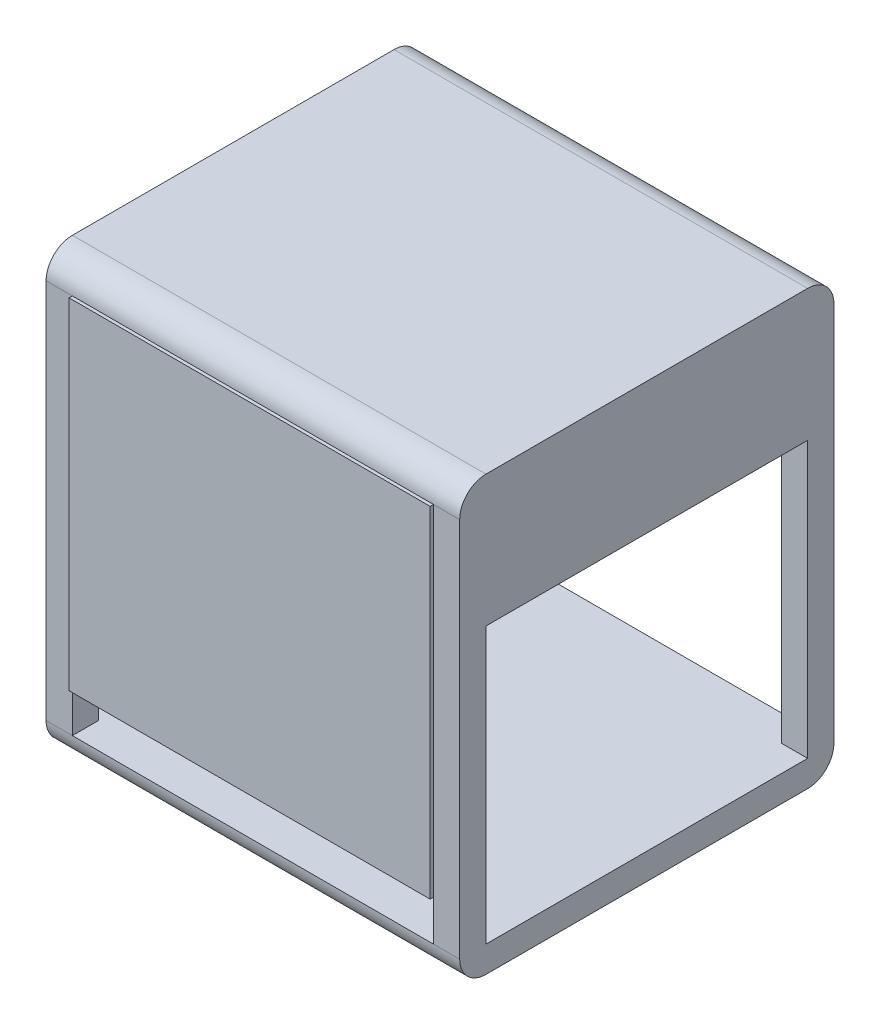
SolidWorks part; units mm, degrees
ref_plane "Front Plane" through (0, 0, 0) normal (0, 0, 1) x (1, 0, 0)
ref_plane "Top Plane" through (0, 0, 0) normal (0, 1, 0) x (1, 0, 0)
ref_plane "Right Plane" through (0, 0, 0) normal (1, 0, 0) x (0, 0, -1)
sketch "Sketch1" plane through (0, 0, 0) normal (0, 1, 0) x (1, 0, 0)
  line L1 (0, 0) -> (630, 0)
  line L2 (0, 0) -> (0, 570)
  line L3 (0, 570) -> (630, 570)
  line L4 (630, 0) -> (630, 570)
extrude "Boss-Extrude1" add sketch "Sketch1" along normal blind 660
ref_plane "Plane1" through (0, 660, 0) normal (0, 1, 0) x (1, 0, 0)
fillet "Fillet1" radius 40 4 edges at (315, 0, -570) (315, 660, -570) (315, 0, 0) (315, 660, 0)
ref_plane "Plane2" through (0, 0, 0) normal (0, 0, 1) x (1, 0, 0)
sketch "Sketch3" plane through (0, 0, 0) normal (0, 0, 1) x (1, 0, 0)
  line L4 (630, 620) -> (0, 620) construction
  line L5 (40, 620) -> (590, 620)
  line L6 (40, 620) -> (40, 40)
  line L7 (40, 40) -> (590, 40)
  line L8 (590, 620) -> (590, 40)
  line L9 (0, 40) -> (630, 40) construction
extrude "Cut-Extrude1" cut sketch "Sketch3" against normal blind 5000 and the other way blind 660
ref_plane "Plane3" through (630, 0, 0) normal (1, 0, 0) x (0, 0, -1)
sketch "Sketch4" plane through (630, 0, 0) normal (1, 0, 0) x (0, 0, -1)
  line L4 (0, 40) -> (570, 40) construction
  line L5 (40, 40) -> (530, 40)
  line L6 (40, 40) -> (40, 459.596)
  line L7 (40, 459.596) -> (530, 459.596)
  line L8 (530, 40) -> (530, 459.596)
extrude "Cut-Extrude2" cut sketch "Sketch4" against normal blind 5000 and the other way blind 5000
ref_plane "Plane4" through (0, 620, 0) normal (0, -1, 0) x (-1, 0, 0)
sketch "Sketch5" plane through (0, 620, 0) normal (0, -1, 0) x (-1, 0, 0)
  line L1 (-11.5968, 374.3051) -> (-612.9435, 374.3051)
  line L2 (-11.5968, 374.3051) -> (-11.5968, 326.7277)
  line L3 (-11.5968, 326.7277) -> (-612.9435, 326.7277)
  line L4 (-612.9435, 374.3051) -> (-612.9435, 326.7277)
extrude "Boss-Extrude2" add sketch "Sketch5" along normal blind 100
ref_plane "Plane5" through (0, 0, -326.7277) normal (0, 0, 1) x (1, 0, 0)
sketch "Sketch6" plane through (0, 0, -326.7277) normal (0, 0, 1) x (1, 0, 0)
  line L0 (590, 620) -> (40, 620) construction
  line L1 (102.7696, 620) -> (181.34, 620)
  line L2 (102.7696, 620) -> (102.7696, 316.9049)
  line L3 (102.7696, 316.9049) -> (181.34, 316.9049)
  line L4 (181.34, 620) -> (181.34, 316.9049)
extrude "Boss-Extrude3" add sketch "Sketch6" against normal blind 10 and the other way blind 50
ref_plane "Plane6" through (0, 316.9049, 0) normal (0, -1, 0) x (-1, 0, 0)
sketch "Sketch7" plane through (0, 316.9049, 0) normal (0, -1, 0) x (-1, 0, 0)
  circle A0 centre (-141.0696, 317.3682) radius 11.2487
extrude "Boss-Extrude4" add sketch "Sketch7" along normal blind 50 draft 8
ref_plane "Plane7" through (0, 0, 0) normal (0, 0, 1) x (1, 0, 0)
sketch "Sketch8" plane through (0, 0, 0) normal (0, 0, 1) x (1, 0, 0)
  line L0 (40, 620) -> (40, 40) construction
  line L1 (590, 620) -> (40, 620)
  line L2 (590, 620) -> (590, 101.8049)
  line L3 (590, 101.8049) -> (40, 101.8049)
  line L4 (40, 620) -> (40, 101.8049)
extrude "Boss-Extrude5" add sketch "Sketch8" along normal blind 5 separate body
